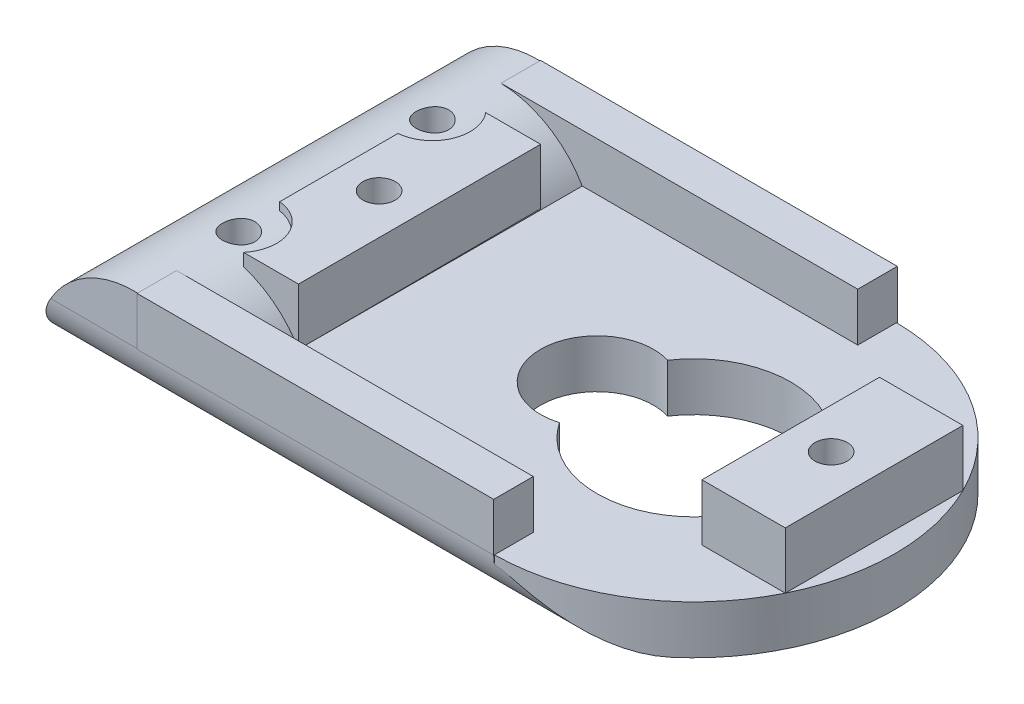
SolidWorks part; units mm, degrees
ref_plane "Alzado" through (0, 0, 0) normal (0, 0, 1) x (1, 0, 0)
ref_plane "Planta" through (0, 0, 0) normal (0, 1, 0) x (1, 0, 0)
ref_plane "Vista lateral" through (0, 0, 0) normal (1, 0, 0) x (0, 0, -1)
sketch "Croquis1" plane through (0, 0, 0) normal (0, 1, 0) x (1, 0, 0)
  line L0 (-20.8175, 12.5739) -> (7.4825, 12.6239)
  line L1 (7.4825, 12.6239) -> (7.4825, 12.5739)
  line L2 (7.4825, -12.3299) -> (7.4825, -12.3761)
  line L3 (7.4825, -12.3761) -> (-20.8175, -12.3261)
  line L4 (-20.8175, -12.3261) -> (-20.8175, 12.5739)
  arc A0 (7.4825, -12.3299) -> (7.4825, 12.5739) centre (7.3742, 0.122) ccw
  arc A1 (2.4033, -3.224) -> (2.4033, 3.4717) centre (7.3825, 0.1239) ccw
  arc A2 (2.4033, 3.4717) -> (2.4033, -3.224) centre (1.3825, 0.1239) ccw
  circle A3 centre (-12.1175, 0.1239) radius 1
  circle A4 centre (-14.8175, 6.1239) radius 1
  circle A5 centre (-14.8175, -5.8761) radius 1
extrude "Saliente-Extruir1" add sketch "Croquis1" along normal blind 3
sketch "Croquis2" plane through (-0.0218, 0, 12.3629) normal (-0.0018, 0, 1) x (1, 0, 0.0018)
  line L0 (-20.7957, 0) -> (7.5044, 0) construction
  line L1 (-9.5995, 3) -> (-19.9918, 3)
  line L2 (-20.7957, 3) -> (7.5044, 3) construction
  arc A0 (-9.5995, 3) -> (-19.9918, 3) centre (-14.7957, 0) ccw
  dimension "D1" = 12
extrude "Saliente-Extruir2" add sketch "Croquis2" against normal up to surface (24.903 mm away) up to face at (-6.6675, 1.5, -12.5989)
sketch "Croquis3" plane through (0, 3, 0) normal (0, 1, 0) x (1, 0, 0)
  line L1 (7.4825, -12.3761) -> (-14.6126, -12.3761)
  line L2 (7.4825, -12.3761) -> (7.4825, -9.9261)
  line L3 (7.4825, -9.9261) -> (-14.6126, -9.9261)
  line L4 (-14.6126, -12.3761) -> (-14.6126, -9.9261)
  line L5 (7.4825, 12.6239) -> (-14.6126, 12.6239)
  line L6 (7.4825, 12.6239) -> (7.4825, 10.1739)
  line L7 (7.4825, 10.1739) -> (-14.6126, 10.1739)
  line L8 (-14.6126, 12.6239) -> (-14.6126, 10.1739)
  line L9 (-13.0126, 7.6239) -> (-9.6126, 7.6239)
  line L10 (-14.6126, 3.786) -> (-14.6126, -3.5382)
  line L11 (-13.0126, -7.3761) -> (-9.6126, -7.3761)
  line L12 (-9.6126, 7.6239) -> (-9.6126, -7.3761)
  line L14 (-9.5773, 12.5937) -> (-9.6214, -12.3459) construction
  line L15 (-20.8175, 12.5739) -> (-20.8175, -12.3261) construction
  line L17 (18.5461, 5.622) -> (13.3825, 5.622)
  line L18 (18.5461, 5.622) -> (18.5461, -5.378)
  line L19 (18.5461, -5.378) -> (13.3825, -5.378)
  line L20 (13.3825, 5.622) -> (13.3825, -5.378)
  arc A0 (-13.0126, -7.3761) -> (-14.6126, -3.5382) centre (-14.8175, -5.8761) ccw
  arc A1 (-14.6126, 3.786) -> (-13.0126, 7.6239) centre (-14.8175, 6.1239) ccw
  arc A2 (7.4825, -12.3299) -> (7.4825, 12.5739) centre (7.3742, 0.122) ccw construction
  arc A3 (2.4033, -3.224) -> (2.4033, 3.4717) centre (7.3825, 0.1239) ccw construction
  circle A4 centre (15.8842, 0.1239) radius 1
  point P17 (-14.6126, 0.1239)
  point P20 (-20.8175, 0.1239)
  point P21 (-13.0126, -7.3761)
  dimension "D4" = 2
  dimension "D1" = 2.45
  dimension "D2" = 3.4
  dimension "D3" = 15
  dimension "D5" = 11
  dimension "D6" = 8.51
extrude "Saliente-Extruir3" add sketch "Croquis3" along normal blind 3
sketch "Croquis4" plane through (0, 6, 0) normal (0, 1, 0) x (1, 0, 0)
  line L4 (18.5461, -5.378) -> (18.5461, 5.622)
  line L5 (18.5461, 5.622) -> (13.3825, 5.622)
  line L6 (13.3825, 5.622) -> (13.3825, -5.378)
  line L7 (13.3825, -5.378) -> (18.5461, -5.378)
  line L8 (18.5461, -5.378) -> (18.5461, 5.622)
  line L9 (18.5461, 5.622) -> (13.3825, 5.622)
  line L10 (13.3825, 5.622) -> (13.3825, -5.378)
  line L11 (13.3825, -5.378) -> (18.5461, -5.378)
  line L12 (-13.0126, -7.3761) -> (-9.6126, -7.3761)
  line L13 (-9.6126, -7.3761) -> (-9.6126, 7.6239)
  line L14 (-9.6126, 7.6239) -> (-13.0126, 7.6239)
  line L15 (-14.6126, 3.786) -> (-14.6126, -3.5382)
  line L16 (-13.0126, -7.3761) -> (-9.6126, -7.3761)
  line L17 (-9.6126, -7.3761) -> (-9.6126, 7.6239)
  line L18 (-9.6126, 7.6239) -> (-13.0126, 7.6239)
  line L19 (-14.6126, 3.786) -> (-14.6126, -3.5382)
  circle A0 centre (15.8842, 0.1239) radius 1 construction
  circle A1 centre (15.8842, 0.1239) radius 1
  arc A4 (-13.0126, -7.3761) -> (-14.6126, -3.5382) centre (-14.8175, -5.8761) ccw
  arc A5 (-14.6126, 3.786) -> (-13.0126, 7.6239) centre (-14.8175, 6.1239) ccw
  arc A6 (-13.0126, -7.3761) -> (-14.6126, -3.5382) centre (-14.8175, -5.8761) ccw
  arc A7 (-14.6126, 3.786) -> (-13.0126, 7.6239) centre (-14.8175, 6.1239) ccw
  dimension "D1" = 0
  dimension "D2" = 0
extrude "Saliente-Extruir4" add sketch "Croquis4" along normal blind 0.5
sketch "Croquis5" plane through (-0.0218, 0, 12.3629) normal (-0.0018, 0, 1) x (1, 0, 0.0018)
  line L0 (-14.6349, 6) -> (-14.6349, 3) construction
  line L1 (7.4602, 0) -> (-20.8397, 0) construction
  line L2 (-14.6349, 5.9973) -> (-14.6349, 8.2296)
  line L3 (-20.7957, 0) -> (-23.0269, 0)
  arc A1 (-14.6349, 5.9978) -> (-20.7957, 0) centre (-14.7957, 0) ccw
  arc A2 (-14.6349, 8.2296) -> (-23.0269, 0) centre (-14.7957, 0) ccw
  arc A3 (-14.6348, 5.9978) -> (-19.9918, 3) centre (-14.7957, 0) ccw construction
  point P4 (0, 0)
  point P15 (0, 0)
  point P16 (-20.7957, 0)
  point P17 (-14.6349, 5.9973)
  arc M4 (-14.5908, 5.9965) -> (-19.9918, 3) centre (-14.7957, 0) ccw
  line M5 (-19.9918, 3) -> (-20.7957, 3)
  line M6 (-20.7957, 3) -> (-20.7957, 0)
  dimension "D1" = 12
extrude "Cortar-Extruir1" cut sketch "Croquis5" against normal blind 30.5 contours L2 A2 L3 M6 M5 M4 | A1 M5 M6 region at (-19.2784, 4.6778, 12.3289) region at (-20.5794, 2.2604, 12.3266)
sketch "Croquis6" plane through (0, 0, 0) normal (0, -1, 0) x (1, 0, 0)
  circle A0 centre (-14.8175, -6.1239) radius 1 construction
  circle A1 centre (-12.1175, -0.1239) radius 1 construction
  circle A2 centre (-14.8175, 5.8761) radius 1 construction
  circle A3 centre (-14.8175, -6.1239) radius 1
  circle A4 centre (-12.1175, -0.1239) radius 1
  circle A5 centre (-14.8175, 5.8761) radius 1
extrude "Cortar-Extruir2" cut sketch "Croquis6" against normal blind 30.5
fillet "Redondeo1" radius 3 2 edges at (-6.6455, 0, -12.5989) (-6.6675, 0, 12.3511)
